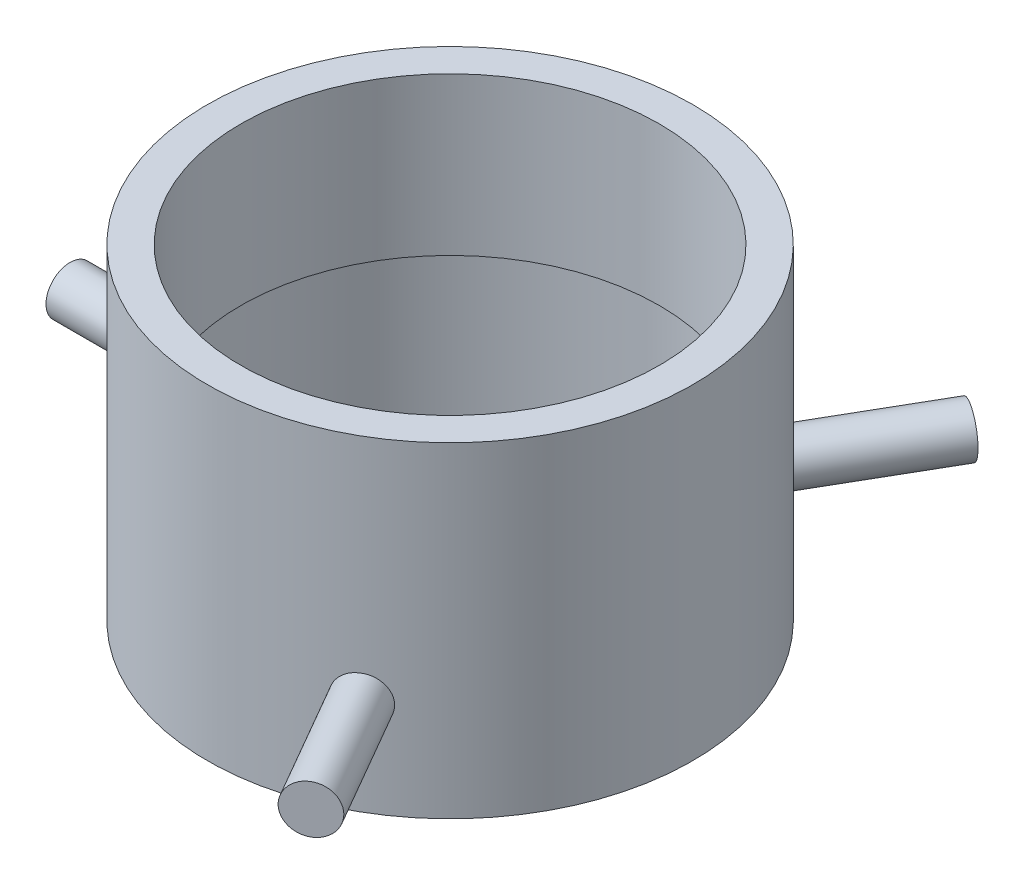
SolidWorks part; units mm, degrees
ref_plane "Front Plane" through (0, 0, 0) normal (0, 0, 1) x (1, 0, 0)
ref_plane "Top Plane" through (0, 0, 0) normal (0, 1, 0) x (1, 0, 0)
ref_plane "Right Plane" through (0, 0, 0) normal (1, 0, 0) x (0, 0, -1)
sketch "Sketch1" plane through (0, 0, 0) normal (0, 0, 1) x (1, 0, 0)
  line L0 (57.15, -44.45) -> (57.15, 0)
  line L1 (57.15, 0) -> (55.245, 0)
  line L2 (55.245, 0) -> (55.245, 41.529)
  line L3 (55.245, 41.529) -> (64.0715, 41.529)
  line L4 (64.0715, 41.529) -> (64.0715, -44.45)
  line L5 (64.0715, -44.45) -> (57.15, -44.45)
  line L6 (55, 0) -> (-55, 0) construction
  line L8 (0, -1015.2582) -> (0, 48984.7418) construction
  dimension "D1" = 114.3
  dimension "D2" = 128.143
  dimension "D3" = 44.45
  dimension "D4" = 85.979
  dimension "D5" = 110.49
revolve "Revolve1" add sketch "Sketch1" angle 360 about L8
sketch "Sketch2" plane through (0, 0, 0) normal (0, 0, 1) x (1, 0, 0)
  line L0 (-1132.0454, -19.05) -> (48867.9546, -19.05) construction
  line L1 (70.4787, 0) -> (-70.4787, 0) construction
  line L2 (-100.33, -12.7) -> (-59.3097, -12.7)
  line L3 (-100.33, -12.7) -> (-100.33, -19.05)
  line L4 (-100.33, -19.05) -> (-59.3097, -19.05)
  line L5 (-59.3097, -12.7) -> (-59.3097, -19.05)
  line L6 (0, -1021.3681) -> (0, 48978.6319) construction
  dimension "D1" = 19.05
  dimension "D2" = 200.66
  dimension "D3" = 12.7
revolve "Revolve2" add sketch "Sketch2" angle 360 about L0
ref_axis "Axis1" through (0, 45.8279, 0) along (0, -1, 0)
pattern_circular "CirPattern1" count 3 over 360 about axis through (0, 45.8279, 0) along (0, -1, 0) of bodies 102
